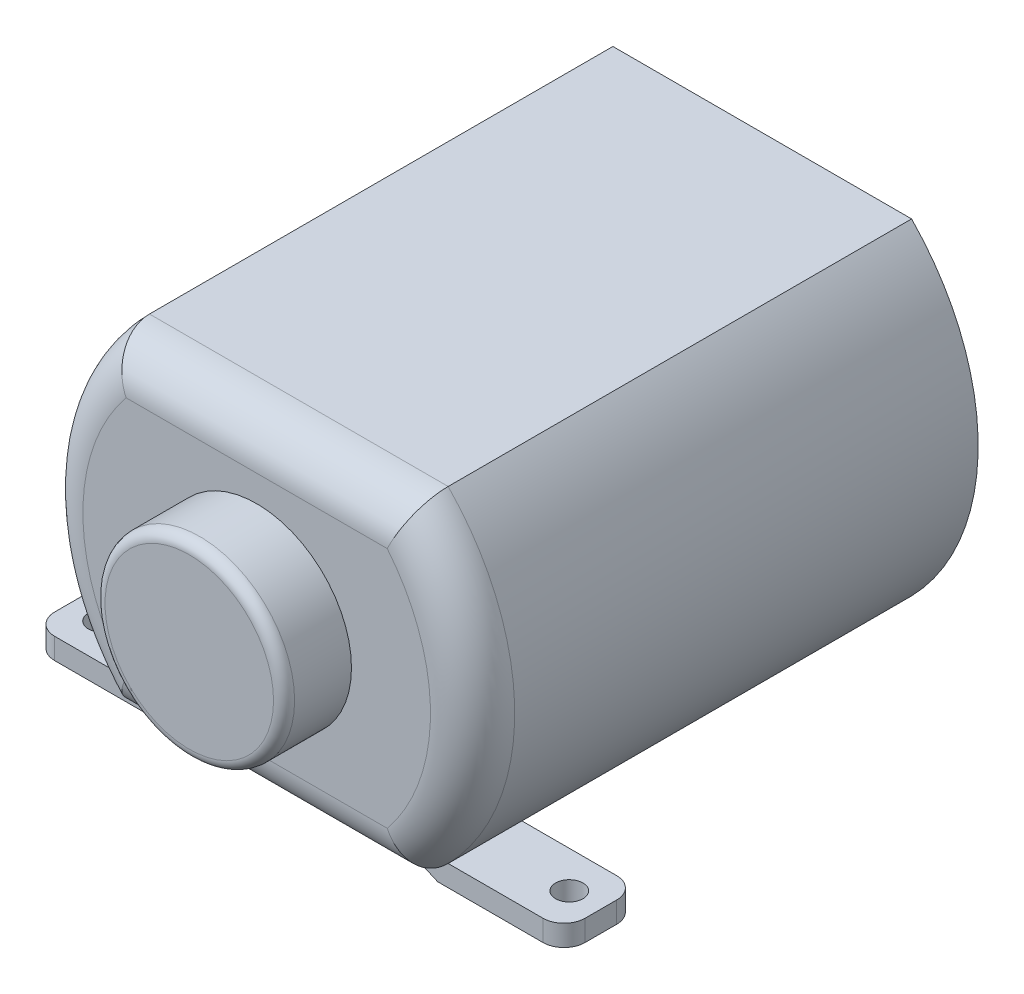
SolidWorks part; units mm, degrees
material "Aleación 1060"
ref_plane "Alzado" through (0, 0, 0) normal (0, 0, 1) x (1, 0, 0)
ref_plane "Planta" through (0, 0, 0) normal (0, 1, 0) x (1, 0, 0)
ref_plane "Vista lateral" through (0, 0, 0) normal (1, 0, 0) x (0, 0, -1)
sketch "Croquis1" plane through (0, 0, 0) normal (0, 0, 1) x (1, 0, 0)
  line L0 (0, 0) -> (0, 7.75) construction
  line L1 (7.09, 7.75) -> (-7.09, 7.75)
  line L2 (0, 0) -> (-10.25, 0) construction
  line L3 (7.09, -7.75) -> (-7.09, -7.75)
  arc A0 (-7.09, 7.75) -> (-7.09, -7.75) centre (0.8336, 0) ccw
  arc A1 (7.09, 7.75) -> (7.09, -7.75) centre (-0.8336, 0) cw
  point P9 (0, -7.75)
  dimension "D1" = 7.09
  dimension "D2" = 3.16
  dimension "D3" = 15.5
extrude "Saliente-Extruir1" add sketch "Croquis1" along normal blind 24
fillet "Redondeo1" radius 2 4 edges at (0, 7.75, 24) (10.25, 0, 24) (0, -7.75, 24) (-10.25, 0, 24)
sketch "Croquis2" plane through (0, 0, 24) normal (0, 0, 1) x (1, 0, 0)
  line L0 (-10.25, 0) -> (10.25, 0) construction
  line L1 (0, 7.75) -> (0, -7.75) construction
  line L2 (-7.09, 7.75) -> (7.09, 7.75) construction
  line L3 (7.09, -7.75) -> (-7.09, -7.75) construction
  arc A0 (-7.09, 7.75) -> (-7.09, -7.75) centre (0.8336, 0) ccw construction
  arc A1 (7.09, -7.75) -> (7.09, 7.75) centre (-0.8336, 0) ccw construction
  circle A2 centre (0, 0) radius 4.5
  dimension "D1" = 9
extrude "Saliente-Extruir2" add sketch "Croquis2" along normal blind 3.2
fillet "Redondeo2" radius 0.5 1 edges at (4.5, 0, 27.2)
sketch "Croquis3" plane through (0, -7.75, 0) normal (0, -1, 0) x (1, 0, 0)
  line L0 (7.09, 22) -> (-7.09, 22) construction
  line L1 (-6.59, 22) -> (-11.59, 22)
  line L2 (-6.59, 22) -> (-6.59, 18.5)
  line L3 (-6.59, 18.5) -> (-11.59, 18.5)
  line L4 (-12.59, 21) -> (-12.59, 19.5)
  line L5 (-7.09, 22) -> (-7.09, 0) construction
  arc A0 (-11.59, 18.5) -> (-12.59, 19.5) centre (-11.59, 19.5) cw
  arc A1 (-12.59, 21) -> (-11.59, 22) centre (-11.59, 21) cw
  circle A2 centre (-11.09, 20.25) radius 0.65
  point P5 (-6.59, 20.25)
  point P14 (-12.59, 22)
  dimension "D4" = 1
  dimension "D5" = 1.3
  dimension "D1" = 0.5
  dimension "D2" = 6
  dimension "D3" = 3.5
  dimension "D6" = 1.5
extrude "Saliente-Extruir3" add sketch "Croquis3" along normal blind 1
fillet "Redondeo3" radius 10 1 edges at (-6.59, -7.75, 20.25)
mirror "Simetría1" about plane through (0, 0, 0) normal (1, 0, 0) of "Saliente-Extruir3", "Redondeo3"
